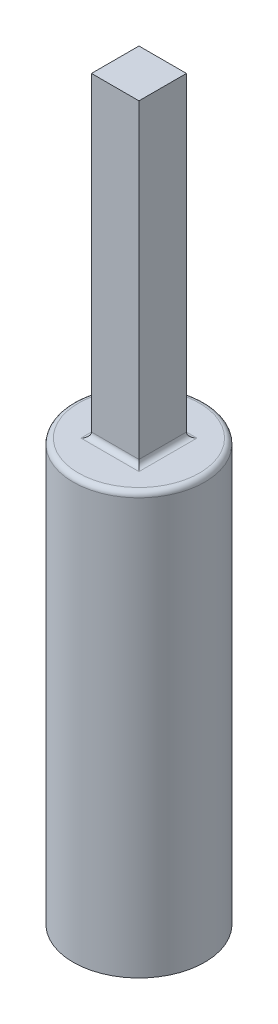
SolidWorks part; units mm, degrees
material "Cast Alloy Steel"
ref_plane "Front Plane" through (0, 0, 0) normal (0, 0, 1) x (1, 0, 0)
ref_plane "Top Plane" through (0, 0, 0) normal (0, 1, 0) x (1, 0, 0)
ref_plane "Right Plane" through (0, 0, 0) normal (1, 0, 0) x (0, 0, -1)
sketch "Sketch2" plane through (0, 0, 0) normal (0, 1, 0) x (1, 0, 0)
  circle A0 centre (0, 0) radius 12.5
  dimension "D1" = 25
extrude "Boss-Extrude1" add sketch "Sketch2" along normal blind 80
sketch "Sketch3" plane through (0, 80, 0) normal (0, 1, 0) x (1, 0, 0)
  line L1 (-4.51, -4.51) -> (4.51, -4.51)
  line L2 (-4.51, -4.51) -> (-4.51, 4.51)
  line L3 (-4.51, 4.51) -> (4.51, 4.51)
  line L4 (4.51, -4.51) -> (4.51, 4.51)
  line L5 (-4.51, -4.51) -> (4.51, 4.51) construction
  line L6 (-4.51, 4.51) -> (4.51, -4.51) construction
  point P0 (0, 0)
  dimension "D1" = 9.02
extrude "Boss-Extrude2" add sketch "Sketch3" along normal blind 60
fillet "Fillet1" radius 1 4 edges at (0, 80, -4.51) (4.51, 80, 0) (-4.51, 80, 0) (0, 80, 4.51)
fillet "Fillet2" radius 1 1 edges at (0, 80, 12.5)
